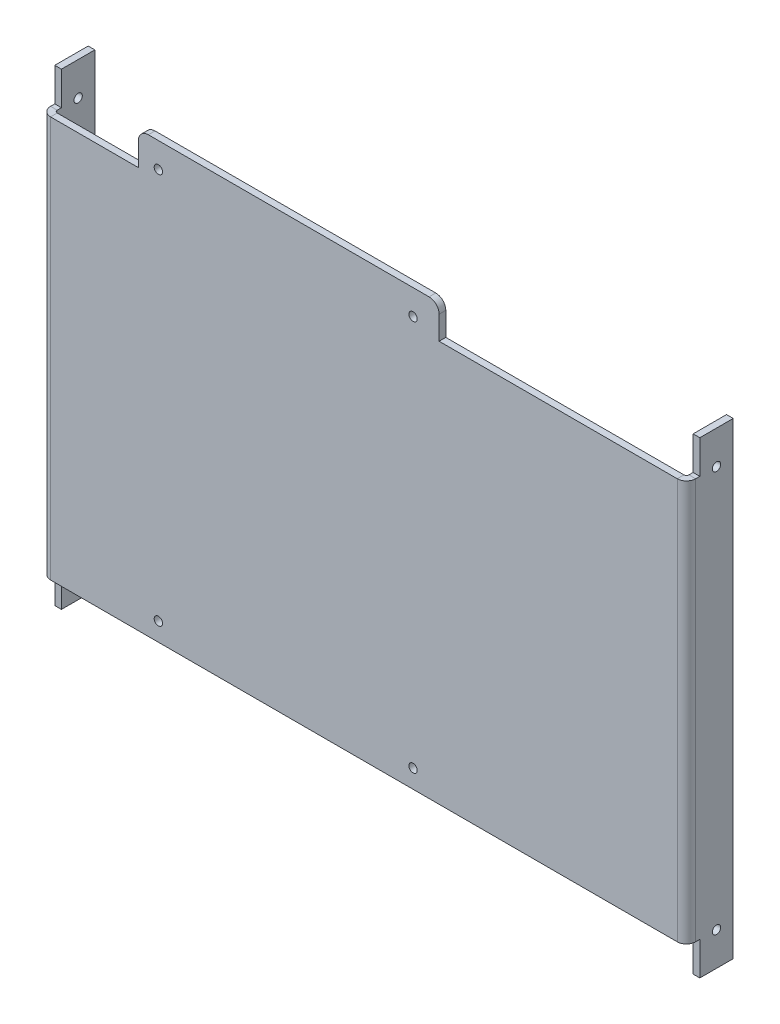
SolidWorks part; units mm, degrees
note: The reader was unsure of these and kept them because the rebuilt part matched: flange length of "ｴｯｼﾞ-ﾌﾗﾝｼﾞ1".
material "5052-H38"
ref_plane "正面" through (0, 0, 0) normal (0, 0, 1) x (1, 0, 0)
ref_plane "平面" through (0, 0, 0) normal (0, 1, 0) x (1, 0, 0)
ref_plane "右側面" through (0, 0, 0) normal (1, 0, 0) x (0, 0, -1)
sketch "ｽｹｯﾁ3" plane through (0, 0, 0) normal (0, 0, 1) x (1, 0, 0)
  line L1 (0, 0) -> (193, 0)
  line L2 (0, 0) -> (0, 140)
  line L3 (0, 140) -> (193, 140)
  line L4 (193, 0) -> (193, 140)
  dimension "D1" = 140
  dimension "D2" = 193
base flange "ﾍﾞｰｽ-ﾌﾗﾝｼﾞ1" sketch "ｽｹｯﾁ3" thickness 2 reverse thickness direction no parameters "D1"=0.7366
edge flange "ｴｯｼﾞ-ﾌﾗﾝｼﾞ1" sketch "ｽｹｯﾁ12" flange profiles "ｽｹｯﾁ12", "ｽｹｯﾁ13" flange angle 90 flange length 14 flange position material inside bend radius 0.7366 thickness 2 relief rectangular parameters "D6"=10, "D8"=1
sketch "ｽｹｯﾁ12" plane through (0, 0, -2) normal (1, 0, 0) x (0, -1, 0)
  line L1 (0, 0) -> (-140, 0) construction
  line L2 (-140, 0) -> (-140, 12)
  line L3 (-140, 12) -> (0, 12)
  line L4 (0, 12) -> (0, 0)
  line L5 (0, 0) -> (-140, 0)
sketch "ｽｹｯﾁ13" plane through (193, 0, -2) normal (-1, 0, 0) x (0, 1, 0)
  line L0 (140, 0) -> (0, 0) construction
  line L1 (140, 0) -> (0, 0)
  line L2 (140, 0) -> (140, 12)
  line L3 (140, 12) -> (0, 12)
  line L4 (0, 12) -> (0, 0)
bend "ｴｯｼﾞﾍﾞﾝﾄﾞ1" bend radius 0.7366 bend angle 90 parameters "D5"=1
bend "ｴｯｼﾞﾍﾞﾝﾄﾞ2" bend radius 0.7366 bend angle 90 parameters "D5"=2
hole_wizard "M3 ねじ穴2" positions "ｽｹｯﾁ18" profile "ｽｹｯﾁ17" tap size "M3" standard "ISO" end condition up to next
sketch "ｽｹｯﾁ18" plane through (0, 0, 0) normal (0, 0, 1) x (1, 0, 0)
  line L1 (0, 0) -> (0, 140) construction
  line L2 (190.2634, 140) -> (2.7366, 140) construction
  point P0 (35, 132.5)
  point P2 (35, 15.5)
  point P4 (111.2, 15.5)
  point P6 (111.2, 132.5)
  dimension "D1" = 76.2
  dimension "D2" = 117
  dimension "D3" = 35
  dimension "D4" = 7.5
sketch "ｽｹｯﾁ17" plane through (35, 132.5, 0) normal (1, 0, 0) x (0, -1, 0)
  line L0 (0, 0) -> (0, 2)
  line L1 (0, 2) -> (1.25, 2)
  line L2 (1.25, 2) -> (1.25, 0)
  line L5 (1.25, 0) -> (0, 0)
  line L11 (0, -6.35) -> (0, 107.95) construction
  dimension "次ｻｰﾌｪｽまでのねじ下穴ﾄﾞﾘﾙ直径" = 2.5
  dimension "次ｻｰﾌｪｽまでのねじ下穴ﾄﾞﾘﾙの深さ" = 2
cosmetic thread "穴のねじ山5"
cosmetic thread "穴のねじ山6"
cosmetic thread "穴のねじ山7"
cosmetic thread "穴のねじ山8"
hole_wizard "M3 ねじ穴3" positions "ｽｹｯﾁ20" profile "ｽｹｯﾁ19" tap size "M3" standard "ISO" end condition up to next
sketch "ｽｹｯﾁ20" plane through (0, 0, 0) normal (-1, 0, 0) x (0, 0, 1)
  line L0 (-14, 0) -> (-14, 140) construction
  line L1 (-14, 140) -> (-2.7366, 140) construction
  point P0 (-9, 130)
  point P2 (-9, 10)
  dimension "D1" = 120
  dimension "D2" = 5
  dimension "D3" = 10
sketch "ｽｹｯﾁ19" plane through (0, 130, -9) normal (0, 1, 0) x (0, 0, 1)
  line L0 (0, 0) -> (0, 2)
  line L1 (0, 2) -> (1.25, 2)
  line L2 (1.25, 2) -> (1.25, 0)
  line L5 (1.25, 0) -> (0, 0)
  line L11 (0, -6.35) -> (0, 107.95) construction
  dimension "次ｻｰﾌｪｽまでのねじ下穴ﾄﾞﾘﾙ直径" = 2.5
  dimension "次ｻｰﾌｪｽまでのねじ下穴ﾄﾞﾘﾙの深さ" = 2
cosmetic thread "穴のねじ山9"
cosmetic thread "穴のねじ山10"
hole_wizard "M3 ねじ穴4" positions "ｽｹｯﾁ22" profile "ｽｹｯﾁ21" tap size "M3" standard "ISO" end condition up to next
sketch "ｽｹｯﾁ22" plane through (193, 0, 0) normal (1, 0, 0) x (0, 0, -1)
  line L0 (2.7366, 140) -> (14, 140) construction
  line L1 (14, 140) -> (14, 0) construction
  point P0 (9, 130)
  point P2 (9, 10)
  dimension "D1" = 10
  dimension "D2" = 120
  dimension "D3" = 5
sketch "ｽｹｯﾁ21" plane through (193, 130, -9) normal (0, 1, 0) x (0, 0, -1)
  line L0 (0, 0) -> (0, 2)
  line L1 (0, 2) -> (1.25, 2)
  line L2 (1.25, 2) -> (1.25, 0)
  line L5 (1.25, 0) -> (0, 0)
  line L11 (0, -6.35) -> (0, 107.95) construction
  dimension "次ｻｰﾌｪｽまでのねじ下穴ﾄﾞﾘﾙ直径" = 2.5
  dimension "次ｻｰﾌｪｽまでのねじ下穴ﾄﾞﾘﾙの深さ" = 2
cosmetic thread "穴のねじ山11"
cosmetic thread "穴のねじ山12"
sketch "ｽｹｯﾁ23" plane through (0, 0, 0) normal (0, 0, 1) x (1, 0, 0)
  line L0 (2.7366, 0) -> (190.2634, 0) construction
  line L1 (4, 10) -> (189, 10)
  line L2 (4, 10) -> (4, 0)
  line L3 (4, 0) -> (189, 0)
  line L4 (189, 10) -> (189, 0)
  line L5 (0, 0) -> (0, 140) construction
  line L6 (193, 0) -> (193, 140) construction
  line L7 (190.2634, 140) -> (2.7366, 140) construction
  line L9 (4, 140) -> (29, 140)
  line L10 (4, 140) -> (4, 130)
  line L11 (4, 130) -> (29, 130)
  line L12 (29, 140) -> (29, 130)
  line L13 (4, 140) -> (29, 130) construction
  line L14 (4, 130) -> (29, 140) construction
  line L15 (189, 140) -> (119, 140)
  line L16 (189, 140) -> (189, 130)
  line L17 (189, 130) -> (119, 130)
  line L18 (119, 140) -> (119, 130)
  line L19 (189, 140) -> (119, 130) construction
  line L20 (189, 130) -> (119, 140) construction
  point P16 (16.5, 135)
  point P21 (154, 135)
  dimension "D1" = 4
  dimension "D2" = 4
  dimension "D3" = 10
  dimension "D4" = 10
  dimension "D5" = 25
  dimension "D6" = 70
extrude "ｶｯﾄ - 押し出し1" cut sketch "ｽｹｯﾁ23" against normal blind 10
fillet "ﾌｨﾚｯﾄ1" radius 3 2 edges at (119, 140, -1) (29, 140, -1)
sketch "ｽｹｯﾁ24" plane through (0, 0, 0) normal (-1, 0, 0) x (0, 0, 1)
  line L0 (-2.7366, 0) -> (-14, 0) construction
  line L1 (-4, 0) -> (0, 0)
  line L2 (-4, 0) -> (-4, 10)
  line L3 (-4, 10) -> (0, 10)
  line L4 (0, 0) -> (0, 10)
  line L5 (-4, 0) -> (0, 10) construction
  line L6 (-4, 10) -> (0, 0) construction
  line L7 (-14, 0) -> (-14, 140) construction
  point P4 (-2, 5)
  dimension "D1" = 10
  dimension "D2" = 10
  dimension "D3" = 4
extrude "ｶｯﾄ - 押し出し2" cut sketch "ｽｹｯﾁ24" against normal through all normal cut yes
sketch "ｽｹｯﾁ25" plane through (0, 0, 0) normal (-1, 0, 0) x (0, 0, 1)
  line L0 (-14, 140) -> (-2.7366, 140) construction
  line L1 (-4, 140) -> (0, 140)
  line L2 (-4, 140) -> (-4, 130)
  line L3 (-4, 130) -> (0, 130)
  line L4 (0, 140) -> (0, 130)
  line L5 (-4, 140) -> (0, 130) construction
  line L6 (-4, 130) -> (0, 140) construction
  line L7 (-14, 0) -> (-14, 140) construction
  point P4 (-2, 135)
  dimension "D1" = 10
  dimension "D2" = 10
  dimension "D3" = 4
extrude "ｶｯﾄ - 押し出し3" cut sketch "ｽｹｯﾁ25" against normal blind 10 normal cut yes
sketch "ｽｹｯﾁ26" plane through (193, 0, 0) normal (1, 0, 0) x (0, 0, -1)
  line L0 (2.7366, 140) -> (14, 140) construction
  line L1 (4, 140) -> (0, 140)
  line L2 (4, 140) -> (4, 130)
  line L3 (4, 130) -> (0, 130)
  line L4 (0, 140) -> (0, 130)
  line L5 (4, 140) -> (0, 130) construction
  line L6 (4, 130) -> (0, 140) construction
  line L7 (14, 140) -> (14, 0) construction
  point P4 (2, 135)
  dimension "D1" = 10
  dimension "D2" = 10
  dimension "D3" = 4
extrude "ｶｯﾄ - 押し出し4" cut sketch "ｽｹｯﾁ26" against normal blind 10 normal cut yes
sketch "ﾍﾞﾝﾄﾞ-ﾗｲﾝ1" [suppressed] plane through (0, 0, 0) normal (0, 1, 0) x (1, 0, 0)
sketch "境界ﾎﾞｯｸｽ1" [suppressed] plane through (0, 0, 0) normal (0, 1, 0) x (1, 0, 0)
sheet metal parameters "板金1" thickness 2 parameters "D1"=0.7366
flat pattern "ﾌﾗｯﾄ-ﾊﾟﾀｰﾝ1" [suppressed]
sketch "ﾍﾞﾝﾄﾞ-ﾗｲﾝ2" plane through (0, 0, 0) normal (0, 1, 0) x (1, 0, 0)
sketch3d "境界ﾎﾞｯｸｽ2" [suppressed]
  line L0 (0, 0, 0) -> (-193, 0, 0) construction
  line L1 (0, 140, 0) -> (-193, 140, 0) construction
  line L2 (0, 0, 0) -> (0, 140, 0) construction
  line L3 (-193, 0, 0) -> (-193, 140, 0) construction
sheet metal parameters "板金2" thickness 2 parameters "D1"=0.7366
flat pattern "ﾌﾗｯﾄ-ﾊﾟﾀｰﾝ1"
sketch "ﾍﾞﾝﾄﾞ-ﾗｲﾝ2" plane through (0, 0, 0) normal (0, 0, 1) x (1, 0, 0)
  line L0 (191.6273, 0) -> (191.6273, 140) construction
  line L1 (1.3727, 140) -> (1.3727, 0) construction
  line L2 (191.6273, 0) -> (191.6273, 140) construction
  line L3 (1.3727, 140) -> (1.3727, 0) construction
sketch3d "境界ﾎﾞｯｸｽ2" [suppressed]
  line L0 (-11.2546, 0, 0) -> (204.2546, 0, 0) construction
  line L1 (-11.2546, 140, 0) -> (204.2546, 140, 0) construction
  line L2 (-11.2546, 0, 0) -> (-11.2546, 140, 0) construction
  line L3 (204.2546, 0, 0) -> (204.2546, 140, 0) construction
bend of the flat pattern "ﾌﾗｯﾄ-<ｴｯｼﾞﾍﾞﾝﾄﾞ1>1"
bend of the flat pattern "ﾌﾗｯﾄ-<ｴｯｼﾞﾍﾞﾝﾄﾞ2>1"
sheet metal parameters "板金4" thickness 2 parameters "D1"=0.7366
flat pattern "ﾌﾗｯﾄ-ﾊﾟﾀｰﾝ1"
sketch "ﾍﾞﾝﾄﾞ-ﾗｲﾝ2" plane through (0, 0, 0) normal (0, 0, 1) x (1, 0, 0)
  line L0 (191.6273, 0) -> (191.6273, 140) construction
  line L1 (1.3727, 140) -> (1.3727, 0) construction
  line L2 (191.6273, 0) -> (191.6273, 140) construction
  line L3 (1.3727, 140) -> (1.3727, 0) construction
sketch3d "境界ﾎﾞｯｸｽ2" [suppressed]
  line L0 (-11.2546, 0, 0) -> (204.2546, 0, 0) construction
  line L1 (-11.2546, 140, 0) -> (204.2546, 140, 0) construction
  line L2 (-11.2546, 0, 0) -> (-11.2546, 140, 0) construction
  line L3 (204.2546, 0, 0) -> (204.2546, 140, 0) construction
bend of the flat pattern "ﾌﾗｯﾄ-<ｴｯｼﾞﾍﾞﾝﾄﾞ1>1"
bend of the flat pattern "ﾌﾗｯﾄ-<ｴｯｼﾞﾍﾞﾝﾄﾞ2>1"
sheet metal parameters "板金5" thickness 2 parameters "D1"=0.7366
flat pattern "ﾌﾗｯﾄ-ﾊﾟﾀｰﾝ1"
sketch "ﾍﾞﾝﾄﾞ-ﾗｲﾝ2" plane through (0, 0, 0) normal (0, 0, 1) x (1, 0, 0)
  line L0 (191.6273, 0) -> (191.6273, 140) construction
  line L1 (1.3727, 140) -> (1.3727, 0) construction
  line L2 (191.6273, 0) -> (191.6273, 140) construction
  line L3 (1.3727, 140) -> (1.3727, 0) construction
sketch3d "境界ﾎﾞｯｸｽ2" [suppressed]
  line L0 (-11.2546, 0, 0) -> (204.2546, 0, 0) construction
  line L1 (-11.2546, 140, 0) -> (204.2546, 140, 0) construction
  line L2 (-11.2546, 0, 0) -> (-11.2546, 140, 0) construction
  line L3 (204.2546, 0, 0) -> (204.2546, 140, 0) construction
bend of the flat pattern "ﾌﾗｯﾄ-<ｴｯｼﾞﾍﾞﾝﾄﾞ1>1"
bend of the flat pattern "ﾌﾗｯﾄ-<ｴｯｼﾞﾍﾞﾝﾄﾞ2>1"
sheet metal parameters "板金6" thickness 2 parameters "D1"=0.7366
flat pattern "ﾌﾗｯﾄ-ﾊﾟﾀｰﾝ1"
sketch "ﾍﾞﾝﾄﾞ-ﾗｲﾝ2" plane through (0, 0, 0) normal (0, 0, 1) x (1, 0, 0)
  line L0 (191.6273, 0) -> (191.6273, 140) construction
  line L1 (1.3727, 140) -> (1.3727, 0) construction
  line L2 (191.6273, 0) -> (191.6273, 140) construction
  line L3 (1.3727, 140) -> (1.3727, 0) construction
sketch3d "境界ﾎﾞｯｸｽ2" [suppressed]
  line L0 (-11.2546, 0, 0) -> (204.2546, 0, 0) construction
  line L1 (-11.2546, 140, 0) -> (204.2546, 140, 0) construction
  line L2 (-11.2546, 0, 0) -> (-11.2546, 140, 0) construction
  line L3 (204.2546, 0, 0) -> (204.2546, 140, 0) construction
bend of the flat pattern "ﾌﾗｯﾄ-<ｴｯｼﾞﾍﾞﾝﾄﾞ1>1"
bend of the flat pattern "ﾌﾗｯﾄ-<ｴｯｼﾞﾍﾞﾝﾄﾞ2>1"
sheet metal parameters "板金7" thickness 2 parameters "D1"=0.7366
flat pattern "ﾌﾗｯﾄ-ﾊﾟﾀｰﾝ1"
sketch "ﾍﾞﾝﾄﾞ-ﾗｲﾝ2" plane through (0, 0, 0) normal (0, 0, 1) x (1, 0, 0)
  line L0 (191.6273, 0) -> (191.6273, 140) construction
  line L1 (1.3727, 140) -> (1.3727, 0) construction
  line L2 (191.6273, 0) -> (191.6273, 140) construction
  line L3 (1.3727, 140) -> (1.3727, 0) construction
sketch3d "境界ﾎﾞｯｸｽ2" [suppressed]
  line L0 (-11.2546, 0, 0) -> (204.2546, 0, 0) construction
  line L1 (-11.2546, 140, 0) -> (204.2546, 140, 0) construction
  line L2 (-11.2546, 0, 0) -> (-11.2546, 140, 0) construction
  line L3 (204.2546, 0, 0) -> (204.2546, 140, 0) construction
bend of the flat pattern "ﾌﾗｯﾄ-<ｴｯｼﾞﾍﾞﾝﾄﾞ1>1"
bend of the flat pattern "ﾌﾗｯﾄ-<ｴｯｼﾞﾍﾞﾝﾄﾞ2>1"
sheet metal parameters "板金8" thickness 2 parameters "D1"=0.7366
flat pattern "ﾌﾗｯﾄ-ﾊﾟﾀｰﾝ1"
sketch "ﾍﾞﾝﾄﾞ-ﾗｲﾝ2" plane through (0, 0, 0) normal (0, 0, 1) x (1, 0, 0)
  line L0 (191.6273, 10) -> (191.6273, 140) construction
  line L1 (1.3727, 140) -> (1.3727, 10) construction
  line L2 (191.6273, 10) -> (191.6273, 140) construction
  line L3 (1.3727, 140) -> (1.3727, 10) construction
sketch3d "境界ﾎﾞｯｸｽ2" [suppressed]
  line L0 (-11.2546, 0, 0) -> (204.2546, 0, 0) construction
  line L1 (-11.2546, 140, 0) -> (204.2546, 140, 0) construction
  line L2 (-11.2546, 0, 0) -> (-11.2546, 140, 0) construction
  line L3 (204.2546, 0, 0) -> (204.2546, 140, 0) construction
bend of the flat pattern "ﾌﾗｯﾄ-<ｴｯｼﾞﾍﾞﾝﾄﾞ1>1"
bend of the flat pattern "ﾌﾗｯﾄ-<ｴｯｼﾞﾍﾞﾝﾄﾞ2>1"
sheet metal parameters "板金9" thickness 2 parameters "D1"=0.7366
flat pattern "ﾌﾗｯﾄ-ﾊﾟﾀｰﾝ1"
sketch "ﾍﾞﾝﾄﾞ-ﾗｲﾝ2" plane through (0, 0, 0) normal (0, 0, 1) x (1, 0, 0)
  line L0 (191.6273, 10) -> (191.6273, 140) construction
  line L1 (1.3727, 130) -> (1.3727, 10) construction
  line L2 (191.6273, 10) -> (191.6273, 140) construction
  line L3 (1.3727, 130) -> (1.3727, 10) construction
sketch3d "境界ﾎﾞｯｸｽ2" [suppressed]
  line L0 (-11.2546, 0, 0) -> (204.2546, 0, 0) construction
  line L1 (-11.2546, 140, 0) -> (204.2546, 140, 0) construction
  line L2 (-11.2546, 0, 0) -> (-11.2546, 140, 0) construction
  line L3 (204.2546, 0, 0) -> (204.2546, 140, 0) construction
bend of the flat pattern "ﾌﾗｯﾄ-<ｴｯｼﾞﾍﾞﾝﾄﾞ1>1"
bend of the flat pattern "ﾌﾗｯﾄ-<ｴｯｼﾞﾍﾞﾝﾄﾞ2>1"
sheet metal parameters "板金10" thickness 2 parameters "D1"=0.7366
flat pattern "ﾌﾗｯﾄ-ﾊﾟﾀｰﾝ1"
sketch "ﾍﾞﾝﾄﾞ-ﾗｲﾝ2" plane through (0, 0, 0) normal (0, 0, 1) x (1, 0, 0)
  line L0 (191.6273, 10) -> (191.6273, 130) construction
  line L1 (1.3727, 130) -> (1.3727, 10) construction
  line L2 (191.6273, 10) -> (191.6273, 130) construction
  line L3 (1.3727, 130) -> (1.3727, 10) construction
sketch3d "境界ﾎﾞｯｸｽ2" [suppressed]
  line L0 (-11.2546, 0, 0) -> (204.2546, 0, 0) construction
  line L1 (-11.2546, 140, 0) -> (204.2546, 140, 0) construction
  line L2 (-11.2546, 0, 0) -> (-11.2546, 140, 0) construction
  line L3 (204.2546, 0, 0) -> (204.2546, 140, 0) construction
bend of the flat pattern "ﾌﾗｯﾄ-<ｴｯｼﾞﾍﾞﾝﾄﾞ1>1"
bend of the flat pattern "ﾌﾗｯﾄ-<ｴｯｼﾞﾍﾞﾝﾄﾞ2>1"
